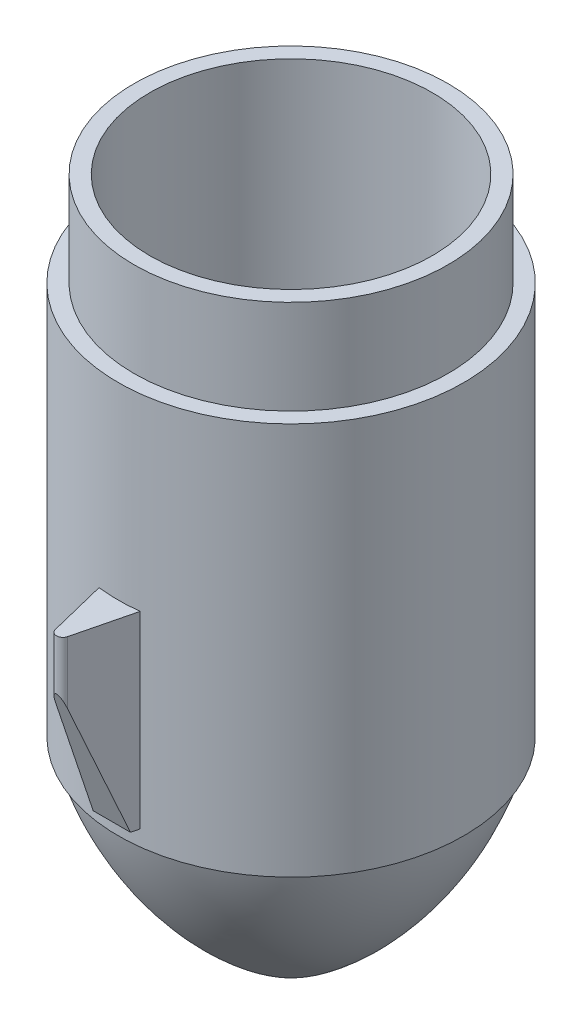
SolidWorks part; units mm, degrees
ref_plane "Front Plane" through (0, 0, 0) normal (0, 0, 1) x (1, 0, 0)
ref_plane "Top Plane" through (0, 0, 0) normal (0, 1, 0) x (1, 0, 0)
ref_plane "Right Plane" through (0, 0, 0) normal (1, 0, 0) x (0, 0, -1)
sketch "Sketch1" plane through (0, 0, 0) normal (0, 1, 0) x (1, 0, 0)
  circle A2 centre (0, 0) radius 45
  dimension "D1" = 90
extrude "Boss-Extrude2" add sketch "Sketch1" along normal blind 150 contours A2
shell "Shell1" thickness 5 removed face at (0, 150, 45) outward yes
sketch "Sketch2" plane through (0, -5, 0) normal (0, -1, 0) x (-1, 0, 0)
  circle A0 centre (0, 0) radius 50
  circle A1 centre (0, 0) radius 55
extrude "Boss-Extrude3" add sketch "Sketch2" against normal blind 125
sketch "Sketch3" plane through (0, 0, 0) normal (0, 0, 1) x (1, 0, 0)
  line L0 (0, 0) -> (0, -70)
  line L1 (0, 0) -> (-55, 0)
  line L2 (-55, 120) -> (-55, -5) construction
  arc A0 (0, -70) -> (-55, 0) centre (44.0101, 21.1865) cw
revolve "Revolve1" add sketch "Sketch3" angle 360 about L0
ref_plane "Plane1" through (0, 60, 0) normal (0, 1, 0) x (1, 0, 0)
sketch "Sketch4" plane through (0, 60, 0) normal (0, 1, 0) x (1, 0, 0)
  line L0 (0, 0) -> (0, 117.9355) construction
  line L1 (6.5428, 54.6094) -> (1.9616, 73.1213)
  line L2 (-6.5428, 54.6094) -> (-1.9616, 73.1213)
  circle A0 centre (0, 0) radius 55 construction
  arc A1 (1.9616, 73.1213) -> (-1.9616, 73.1213) centre (0, 72.6518) ccw
  arc A2 (6.5428, 54.6094) -> (-6.5428, 54.6094) centre (0, 0) ccw
extrude "Boss-Extrude4" add sketch "Sketch4" against normal blind 60
sketch "Sketch5" plane through (0, 0, 0) normal (1, 0, 0) x (0, 0, -1)
  line L0 (74.6687, 43.9407) -> (56.0242, -2.6223)
  line L1 (74.6687, 0) -> (74.6687, 60) construction
  line L2 (56.0242, -2.6223) -> (78.7969, -2.6223)
  line L3 (78.7969, -2.6223) -> (78.7969, 43.9407)
  line L4 (78.7969, 43.9407) -> (74.6687, 43.9407)
extrude "Cut-Extrude1" cut sketch "Sketch5" against normal mid plane 15
pattern_circular "CirPattern1" count 2 over 360 about axis through (0, 120, 0) along (0, -1, 0) of "Boss-Extrude4" reverse direction yes
pattern_circular "CirPattern2" count 2 over 360 about axis through (0, 120, 0) along (0, -1, 0) of "Cut-Extrude1" reverse direction yes
